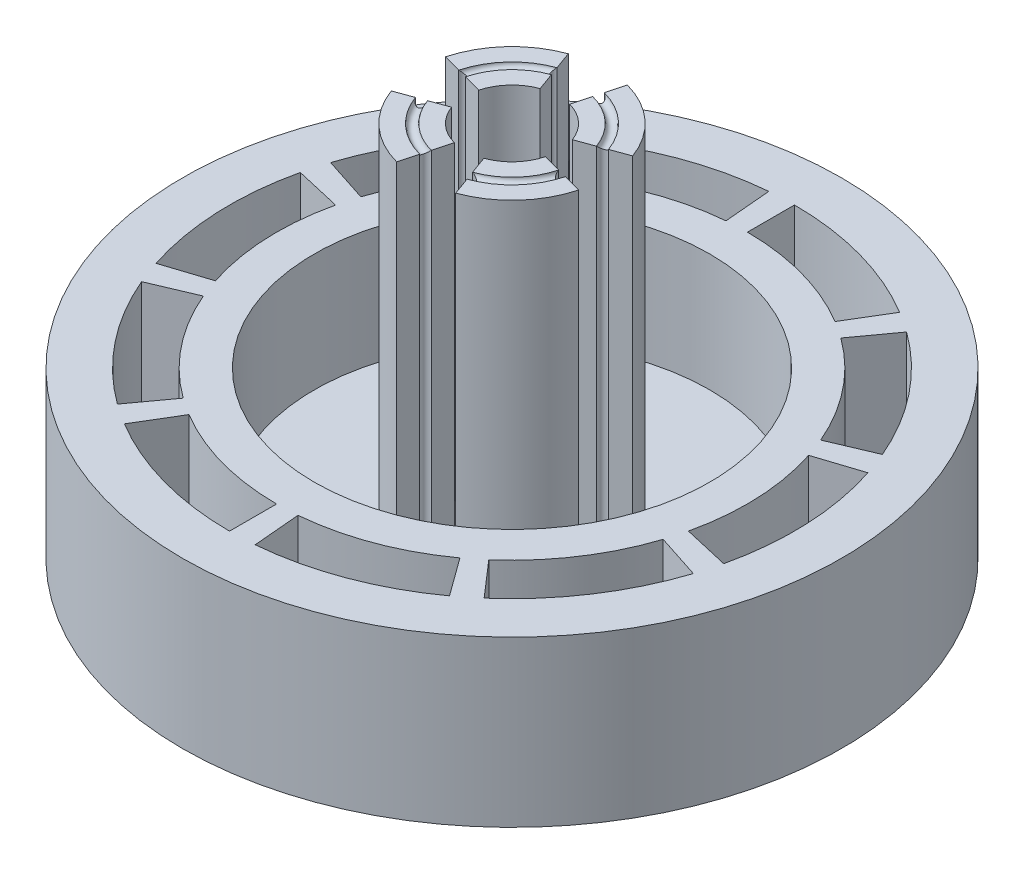
SolidWorks part; units mm, degrees
ref_plane "Front Plane" through (0, 0, 0) normal (0, 0, 1) x (1, 0, 0)
ref_plane "Top Plane" through (0, 0, 0) normal (0, 1, 0) x (1, 0, 0)
ref_plane "Right Plane" through (0, 0, 0) normal (1, 0, 0) x (0, 0, -1)
sketch "Sketch2" plane through (0, 0, 0) normal (0, 1, 0) x (1, 0, 0)
  line L0 (-17.6336, -24.2705) -> (-35.2671, -48.541)
  line L1 (-15.4511, -25.715) -> (-30.9023, -51.43)
  line L3 (-27.6151, -11.7219) -> (-55.2303, -23.4439)
  line L4 (-28.5317, 9.2705) -> (-57.0634, 18.541)
  line L6 (-17.6336, 24.2705) -> (-35.2671, 48.541)
  line L7 (-19.6818, 22.6413) -> (-39.3635, 45.2826)
  line L8 (0, 30) -> (0, 60)
  line L9 (-2.6147, 29.8858) -> (-5.2293, 59.7717)
  line L10 (17.6336, 24.2705) -> (35.2671, 48.541)
  line L11 (15.4511, 25.715) -> (30.9023, 51.43)
  line L13 (27.6151, 11.7219) -> (55.2303, 23.4439)
  line L14 (28.5317, -9.2705) -> (57.0634, -18.541)
  line L16 (17.6336, -24.2705) -> (35.2671, -48.541)
  line L17 (19.6818, -22.6413) -> (39.3635, -45.2826)
  line L21 (-28.5317, -9.2705) -> (-57.0634, -18.541)
  line L23 (-29.2311, 6.7485) -> (-58.4622, 13.4971)
  line L24 (28.5317, 9.2705) -> (57.0634, 18.541)
  line L25 (0, -30) -> (0, -60)
  line L26 (29.2311, -6.7485) -> (58.4622, -13.4971)
  line L27 (2.6147, -29.8858) -> (5.2293, -59.7717)
  line L28 (-9.3969, -3.4202) -> (-18.7939, -6.8404)
  line L29 (-9.6593, 2.5882) -> (-19.3185, 5.1764)
  line L30 (2.5882, 9.6593) -> (5.1764, 19.3185)
  line L31 (-3.4202, 9.3969) -> (-6.8404, 18.7939)
  line L32 (9.6593, -2.5882) -> (19.3185, -5.1764)
  line L33 (9.3969, 3.4202) -> (18.7939, 6.8404)
  line L34 (-2.5882, -9.6593) -> (-5.1764, -19.3185)
  line L35 (3.4202, -9.3969) -> (6.8404, -18.7939)
  line L36 (9.5106, 3.0902) -> (19.0211, 6.1803) [skipped]
  line L37 (9.7437, -2.2495) -> (19.4874, -4.499) [skipped]
  line L38 (-9.5106, -3.0902) -> (-19.0211, -6.1803) [skipped]
  line L39 (-9.7437, 2.2495) -> (-19.4874, 4.499) [skipped]
  circle A0 centre (0, 0) radius 50
  circle A1 centre (0, 0) radius 60
  circle A2 centre (0, 0) radius 42
  circle A3 centre (0, 0) radius 30
  circle A4 centre (0, 0) radius 20
  circle A5 centre (0, 0) radius 10
  circle A6 centre (0, 0) radius 70
  circle A7 centre (0, 0) radius 38
  point P51 (0, 0)
  point P52 (0, 0)
  point P64 (0, 0)
  point P80 (0, 0)
  dimension "D1" = 10
extrude "Boss-Extrude2" add sketch "Sketch2" along normal blind 35 contours A6 A1 | A2 L25 A0 L27 | A2 L27 A0 L16 | A2 L16 A0 L17 | A2 L17 A0 L14 | A2 L1 A0 L25 | A2 L0 A0 L1 | A2 L3 A0 L0 | A2 A0 L3 | A2 A0 | A2 L4 A0 | A2 L7 A0 L4 | A2 L6 A0 L7 | A2 L9 A0 L6 | A2 L8 A0 L9 | A2 L11 A0 L8 | A2 L10 A0 L11 | A2 L13 A0 L10 | A2 L14 A0 | A2 A0 | A2 A0 L13 | L25 A1 L27 A0 | L16 A1 L17 A0 | L14 A1 A0 | A1 L13 A0 | L10 A1 L11 A0 | L8 A1 L9 A0 | L6 A1 L7 A0 | L4 A1 A0 | A1 L3 A0 | L0 A1 L1 A0 region at (-25.445, 0, 38.4432) region at (-35.6521, 0, 28.359) region at (-30.4305, 0, 45.9755) region at (-43.1818, 0, 16.145) region at (-12.1742, 0, 43.8987) region at (-51.6425, 0, 19.3083) region at (-45.5121, 0, 1.9871) region at (2.0109, 0, 46.0574) region at (2.4049, 0, 55.0815) region at (-44.4246, 0, -12.32) region at (15.9539, 0, 42.6706) region at (-53.1288, 0, -14.7339) region at (-37.9881, 0, -25.1438) region at (28.6987, 0, 36.0793) region at (34.3217, 0, 43.1483) region at (-28.6987, 0, -36.0793) region at (37.9881, 0, 25.1438) region at (-34.3217, 0, -43.1483) region at (-15.9539, 0, -42.6706) region at (44.4246, 0, 12.32) region at (53.1288, 0, 14.7339) region at (-2.0109, 0, -46.0574) region at (45.5121, 0, -1.9871) region at (-2.4049, 0, -55.0815) region at (12.1742, 0, -43.8987) region at (25.445, 0, -38.4432) region at (43.1818, 0, -16.145) region at (30.4305, 0, -45.9755) region at (51.6425, 0, -19.3083) region at (35.6521, 0, -28.359) region at (-68.0201, 0, 0)
extrude "Boss-Extrude3" add sketch "Sketch2<10>" along normal blind 80 contours A5 L28 A4 L34 | A5 L31 A4 L29 | A5 L33 A4 L30 | A5 L35 A4 L32 region at (-10.1103, 0, 11.0335) region at (11.0335, 0, 10.1103) region at (-11.0335, 0, -10.1103) region at (10.1103, 0, -11.0335)
sketch "Sketch2<10>" plane through (0, 0, 0) normal (0, 1, 0) x (1, 0, 0) same geometry as "Sketch2"
sketch "Sketch1" plane through (0, 0, 0) normal (0, 1, 0) x (1, 0, 0)
  circle A0 centre (0, 0) radius 50
  circle A1 centre (0, 0) radius 20
extrude "Boss-Extrude4" add sketch "Sketch1" along normal blind 10
sketch "Sketch3" plane through (0, 80, 0) normal (0, 1, 0) x (1, 0, 0)
  line L0 (13.523, -3.6235) -> (15.4548, -4.1411)
  line L1 (-3.6235, -13.523) -> (-4.1411, -15.4548)
  line L2 (4.7883, -13.1557) -> (5.4723, -15.0351)
  line L3 (-13.1557, -4.7883) -> (-15.0351, -5.4723)
  line L4 (-13.523, 3.6235) -> (-15.4548, 4.1411)
  line L5 (-4.7883, 13.1557) -> (-5.4723, 15.0351)
  line L6 (3.6235, 13.523) -> (4.1411, 15.4548)
  line L7 (13.1557, 4.7883) -> (15.0351, 5.4723)
  line L11 (3.4202, -9.3969) -> (6.8404, -18.7939) construction
  arc A0 (5.4723, -15.0351) -> (4.7883, -13.1557) centre (5.1303, -14.0954) ccw
  arc A2 (15.4548, -4.1411) -> (13.523, -3.6235) centre (14.4889, -3.8823) cw
  arc A3 (-15.0351, -5.4723) -> (-13.1557, -4.7883) centre (-14.0954, -5.1303) ccw
  arc A4 (-4.1411, -15.4548) -> (-3.6235, -13.523) centre (-3.8823, -14.4889) cw
  arc A5 (-5.4723, 15.0351) -> (-4.7883, 13.1557) centre (-5.1303, 14.0954) ccw
  arc A6 (-15.4548, 4.1411) -> (-13.523, 3.6235) centre (-14.4889, 3.8823) cw
  arc A7 (15.0351, 5.4723) -> (13.1557, 4.7883) centre (14.0954, 5.1303) ccw
  arc A8 (4.1411, 15.4548) -> (3.6235, 13.523) centre (3.8823, 14.4889) cw
  point P29 (0, 0)
extrude "Cut-Extrude1" cut sketch "Sketch3" against normal up to next
sketch "Sketch5" plane through (0, 0, 0) normal (0.9659, 0, 0.2588) x (0.2588, 0, -0.9659)
  line L0 (-14, 80) -> (-16, 80)
  line L1 (0, 80) -> (0, 75)
  arc A0 (-16, 80) -> (-14, 80) centre (-15, 80) ccw
revolve "Cut-Revolve1" cut sketch "Sketch5" angle 360 about L1 region at (-3.8823, 79.5756, 14.4889)
sketch "Sketch7" plane through (0, 80, 0) normal (0, 1, 0) x (1, 0, 0)
  line L0 (0, 0) -> (7.3728, -6.7559)
  arc A0 (3.4202, -9.3969) -> (9.6593, -2.5882) centre (0, 0) ccw construction
